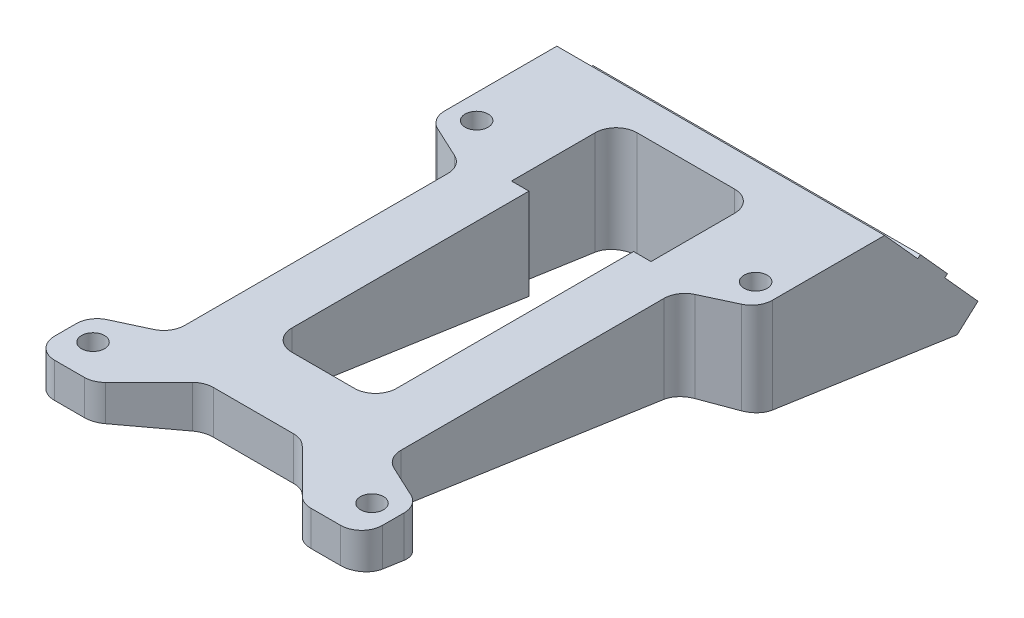
SolidWorks part; units mm, degrees
ref_plane "前视基准面" through (0, 0, 0) normal (0, 0, 1) x (1, 0, 0)
ref_plane "上视基准面" through (0, 0, 0) normal (0, 1, 0) x (1, 0, 0)
ref_plane "右视基准面" through (0, 0, 0) normal (1, 0, 0) x (0, 0, -1)
sketch "草图2" plane through (0, 0, 0) normal (0, 1, 0) x (1, 0, 0)
  line L0 (0, 0) -> (23.5, 0)
  line L1 (23.5, 0) -> (23.5, -14)
  line L4 (23.5, -75) -> (0, -75)
  line L5 (0, -75) -> (0, 0)
  line L6 (23.5, -14) -> (23.5, -75)
  dimension "D1" = 23.5
  dimension "D2" = 75
  dimension "D3" = 23.5
  dimension "D4" = 23.5
  dimension "D6" = 61
extrude "凸台-拉伸2" add sketch "草图2" along normal blind 5
mirror "镜向1" about plane through (0, 5, 75) normal (1, 0, 0) of "凸台-拉伸2"
sketch "草图3" plane through (0, 5, 0) normal (0, 1, 0) x (1, 0, 0)
  line L0 (-41.875, -15) -> (42.0058, -15) construction
  line L1 (-48.5488, -70) -> (45.2773, -70) construction
  line L2 (-20, 7.7517) -> (-20, -80.1072) construction
  line L3 (20, 7.7517) -> (20, -77.5947) construction
  line L4 (-23.5, -75) -> (23.5, -75) construction
  circle A0 centre (-20, -15) radius 1.65
  circle A1 centre (20, -15) radius 1.65
  circle A2 centre (-20, -70) radius 1.65
  circle A3 centre (20, -70) radius 1.65
  point P10 (0, -75)
  dimension "D5" = 3.3
  dimension "D1" = 5
  dimension "D2" = 55
  dimension "D3" = 40
  dimension "D4" = 20
extrude "切除-拉伸1" cut sketch "草图3" against normal through all
sketch "草图5" plane through (0, 0, 0) normal (1, 0, 0) x (0, 0, -1)
  line L0 (-75, 0) -> (10.41, -12.5394)
  line L1 (10.41, -12.5394) -> (13.3826, -9.8629)
  line L2 (13.3826, -9.8629) -> (0, 5)
  line L3 (0, 5) -> (0, 0) construction
  line L4 (-75, 0) -> (0, 0) construction
  line L5 (0, 5) -> (0, 0)
  line L6 (-75, 0) -> (0, 0)
  line L7 (4.7508, -0.2763) -> (8.6318, -4.5866)
  line L8 (4.7508, -0.2763) -> (5.1224, 0.0582)
  line L9 (8.6318, -4.5866) -> (9.0034, -4.252)
  line L10 (5.1224, 0.0582) -> (9.0034, -4.252)
  line L11 (7.0629, -2.0969) -> (3.8382, -5.0004) construction
  dimension "D1" = 20
  dimension "D2" = 4
  dimension "D3" = 42
  dimension "D4" = 10
  dimension "D5" = 5.8
  dimension "D6" = 0.5
extrude "凸台-拉伸3" add sketch "草图5" along normal mid plane 47 contours L6 L0 L1 L2 L7 L5 | L11 L10 L8 L7 | L10 L11 L2 L9 region at (0, -4.2198, 18.1192) region at (0, -3.3417, -7.8473) region at (0, -1.1866, -5.9069)
sketch "草图6" plane through (0, 2.5732, -2.8579) normal (0, 0.6691, -0.7431) x (1, 0, 0)
  line L0 (-23.5, 6.2843) -> (23.5, 6.2843) construction
  line L1 (-23.5, 3.3843) -> (-23.5, 9.1843) construction
  line L2 (23.5, 3.3843) -> (23.5, 9.1843) construction
  line L3 (-13.5, 9.1843) -> (-13.5, 3.3843) construction
  line L4 (23.5, 9.1843) -> (-23.5, 9.1843) construction
  line L5 (23.5, 3.3843) -> (-23.5, 3.3843) construction
  line L6 (13.5, 9.1843) -> (13.5, 3.3843) construction
  line L7 (23.5, 9.1843) -> (-23.5, 9.1843) construction
  line L8 (23.5, 3.3843) -> (-23.5, 3.3843) construction
  circle A0 centre (-13.5, 6.2843) radius 2.6
  circle A1 centre (13.5, 6.2843) radius 2.6
  dimension "D3" = 5.2
  dimension "D1" = 10
  dimension "D2" = 10
extrude "切除-拉伸3" cut sketch "草图6" against normal through all
sketch "草图7" plane through (0, 2.5732, -2.8579) normal (0, 0.6691, -0.7431) x (1, 0, 0)
  circle A0 centre (-13.5, 6.2843) radius 4.5
  circle A1 centre (13.5, 6.2843) radius 4.5
  dimension "D1" = 9
extrude "切除-拉伸4" cut sketch "草图7" against normal up to next from offset 5 offset against normal yes
sketch "草图8" plane through (0, 5, 0) normal (0, -1, 0) x (1, 0, 0)
  circle A0 centre (-20, 15) radius 3
  circle A1 centre (20, 15) radius 3
  circle A2 centre (20, 70) radius 3
  circle A3 centre (-20, 70) radius 3
  dimension "D1" = 6
extrude "切除-拉伸5" cut sketch "草图8" along normal up to next from offset 3
sketch "草图4" plane through (0, 5, 0) normal (0, 1, 0) x (1, 0, 0)
  line L0 (-23.5, -75) -> (23.5, -75) construction
  line L1 (-7.5, -5) -> (7.5, -5)
  line L2 (-7.5, -5) -> (-7.5, -57)
  line L3 (-7.5, -57) -> (7.5, -57)
  line L4 (7.5, -5) -> (7.5, -57)
  line L5 (-15, -75) -> (-7, -67)
  line L6 (-7, -67) -> (7, -67)
  line L7 (7, -67) -> (15, -75)
  line L8 (15, -75) -> (-15, -75)
  line L9 (-23.5, -67) -> (-15.5, -63.2695)
  line L10 (-23.5, -75) -> (-23.5, 0) construction
  line L11 (-15.5, -63.2695) -> (-15.5, -21.7305)
  line L12 (-15.5, -21.7305) -> (-23.5, -18)
  line L13 (-23.5, -18) -> (-23.5, -67)
  line L14 (-23.5, -75) -> (23.5, -75) construction
  line L15 (23.5, 0) -> (-23.5, 0) construction
  line L16 (0, 0) -> (0, -5.79) construction
  line L17 (15.5, -21.7305) -> (23.5, -18)
  line L18 (15.5, -63.2695) -> (15.5, -21.7305)
  line L19 (23.5, -67) -> (15.5, -63.2695)
  line L20 (23.5, -18) -> (23.5, -67)
  line L22 (-10, -5) -> (10, -5)
  line L23 (-10, -5) -> (-10, -20)
  line L24 (-10, -20) -> (10, -20)
  line L25 (10, -5) -> (10, -20)
  point P6 (0, -75)
  point P10 (0, -75)
  point P33 (0, -5)
  line M9 (-23.5, 0) -> (-23.5, -75)
  line M15 (-23.5, -75) -> (23.5, -75)
  line M28 (23.5, -75) -> (23.5, 0)
  dimension "D1" = 18
  dimension "D2" = 52
  dimension "D3" = 15
  dimension "D4" = 7.5
  dimension "D5" = 30
  dimension "D6" = 8
  dimension "D7" = 45
  dimension "D8" = 45
  dimension "D9" = 8
  dimension "D10" = 18
  dimension "D11" = 8
  dimension "D12" = 65
  dimension "D13" = 65
  dimension "D14" = 20
  dimension "D15" = 15
extrude "切除-拉伸2" cut sketch "草图4" against normal through all contours L11 L12 L9 M9 | L19 L17 L18 M28 | L7 L6 L5 M15 | L24 L2 L3 L4 | L24 L25 L22 L23 region at (0, 5, 38.5) region at (19.6099, 5, 42.5) region at (0, 5, 71.4848) region at (-19.6099, 5, 42.5)
fillet "圆角1" radius 3 18 edges at (7.5, 1.1787, 57) (-7.5, 1.1787, 57) (23.5, -1.6842, 18) (15.5, -1.4104, 21.7305) (15.5, 1.6389, 63.2695) (23.5, 1.9127, 67) (23.5, 2.5, 75) (15, 2.5, 75) (7, 1.9127, 67) (-7, 1.9127, 67) (-15, 2.5, 75) (-23.5, 2.5, 75) (-23.5, 1.9127, 67) (-15.5, 1.6389, 63.2695) (-15.5, -1.4104, 21.7305) (-23.5, -1.6842, 18) (10, -2.0762, 5) (-10, -2.0762, 5)
